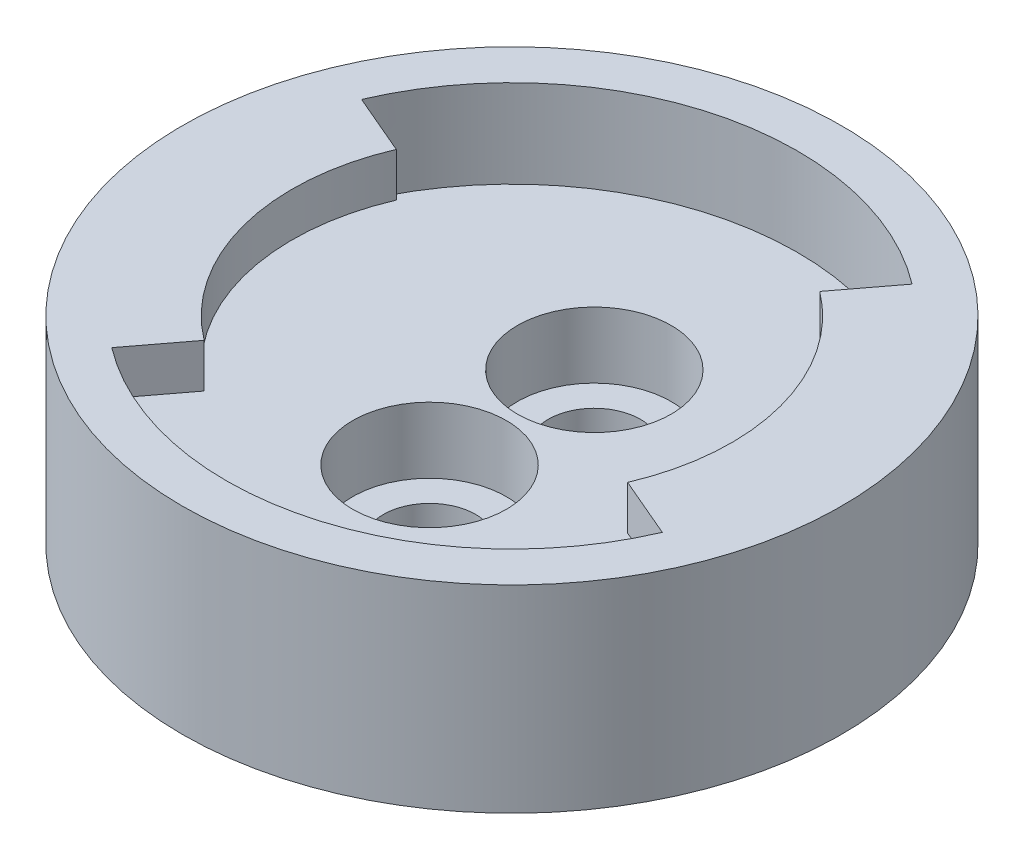
SolidWorks part; units mm, degrees
ref_plane "Ebene vorne" through (0, 0, 0) normal (0, 0, 1) x (1, 0, 0)
ref_plane "Ebene oben" through (0, 0, 0) normal (0, 1, 0) x (1, 0, 0)
ref_plane "Ebene rechts" through (0, 0, 0) normal (1, 0, 0) x (0, 0, -1)
sketch "Skizze1" plane through (0, 0, 0) normal (0, 1, 0) x (1, 0, 0)
  circle A0 centre (0, 0) radius 15
  dimension "D1" = 30
extrude "Aufsatz-Linear austragen1" add sketch "Skizze1" against normal blind 5
sketch "Skizze2" plane through (0, 0, 0) normal (0, 1, 0) x (1, 0, 0)
  circle A0 centre (0, 0) radius 15
  circle A1 centre (0, 0) radius 13
  dimension "D1" = 26
extrude "Aufsatz-Linear austragen2" add sketch "Skizze2" along normal blind 4
sketch "Skizze3" plane through (0, 4, 0) normal (0, 1, 0) x (1, 0, 0)
  line L0 (0, 0) -> (21.5569, -9.2148) construction
  line L1 (0, 0) -> (-22.5777, 9.6512) construction
  line L2 (0, 0) -> (14.6044, 19.2602) construction
  line L3 (0, 0) -> (-17.7821, -23.451) construction
  line L4 (-6.0421, -7.9683) -> (-7.8547, -10.3587)
  line L5 (-9.1951, 3.9306) -> (-11.9537, 5.1098)
  line L6 (6.0421, 7.9683) -> (7.8547, 10.3587)
  line L7 (9.1951, -3.9306) -> (11.9537, -5.1098)
  arc A0 (7.8547, 10.3587) -> (11.9537, -5.1098) centre (0, 0) cw
  circle A1 centre (0, 0) radius 13 construction
  arc A2 (6.0421, 7.9683) -> (9.1951, -3.9306) centre (0, 0) cw
  arc A3 (-11.9537, 5.1098) -> (-7.8547, -10.3587) centre (0, 0) ccw
  arc A4 (-9.1951, 3.9306) -> (-6.0421, -7.9683) centre (0, 0) ccw
extrude "Aufsatz-Linear austragen3" add sketch "Skizze3" against normal blind 2
sketch "Skizze5" plane through (0, 0, 0) normal (0, 1, 0) x (1, 0, 0)
  line L0 (0, 0) -> (0, 3.75) construction
  line L1 (0, 0) -> (0, -3.75) construction
  circle A0 centre (0, 3.75) radius 3.5
  circle A1 centre (0, -3.75) radius 3.5
  dimension "D1" = 3.75
extrude "Schnitt-Linear austragen1" cut sketch "Skizze5" against normal blind 3
sketch "Skizze6" plane through (0, -3, 0) normal (0, 1, 0) x (1, 0, 0)
  line L0 (0, 0) -> (0, 3.75) construction
  line L1 (0, 0) -> (0, -3.75) construction
  circle A0 centre (0, 3.75) radius 2.1
  circle A1 centre (0, -3.75) radius 2.1
extrude "Schnitt-Linear austragen2" cut sketch "Skizze6" against normal blind 3
